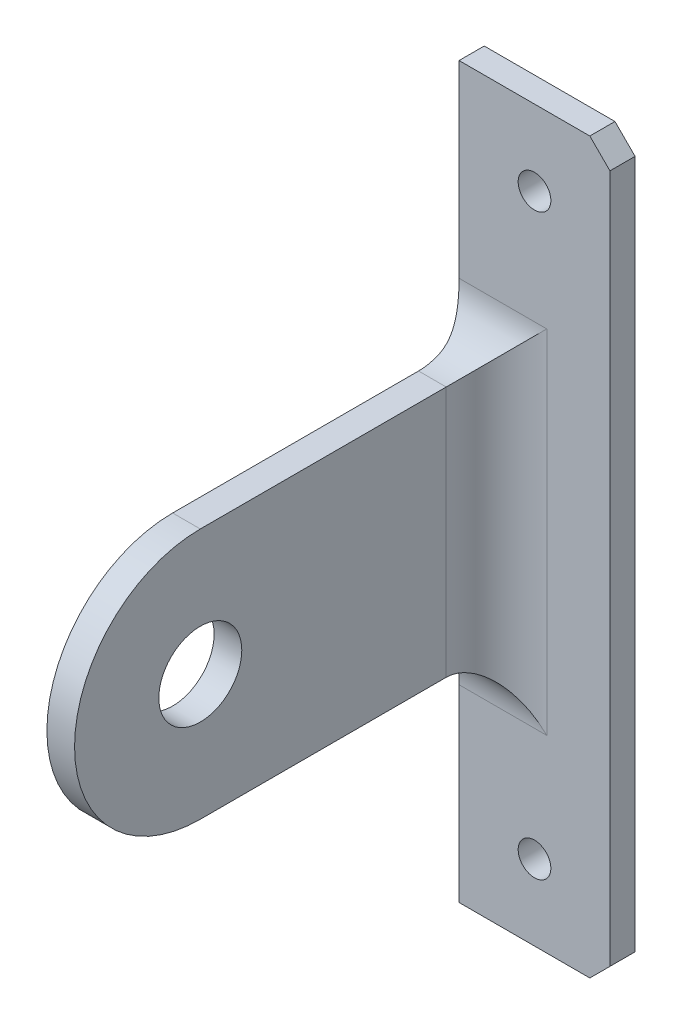
SolidWorks part; units mm, degrees
ref_plane "Front Plane" through (0, 0, 0) normal (0, 0, 1) x (1, 0, 0)
ref_plane "Top Plane" through (0, 0, 0) normal (0, 1, 0) x (1, 0, 0)
ref_plane "Right Plane" through (0, 0, 0) normal (1, 0, 0) x (0, 0, -1)
sketch "Sketch1" plane through (0, 0, 0) normal (1, 0, 0) x (0, 0, -1)
  line L1 (0, 12.5) -> (34.45, 12.5)
  line L2 (0, 4.125) -> (0, -12.5)
  line L3 (0, -12.5) -> (34.45, -12.5)
  line L4 (34.45, 12.5) -> (34.45, -12.5)
  circle A0 centre (0, 0) radius 4.125
  circle A1 centre (0, 0) radius 12.5 construction
  arc A2 (0, 12.5) -> (0, -12.5) centre (0, 0) ccw
  dimension "D1" = 8.25
  dimension "D2" = 25
  dimension "D3" = 34.45
extrude "Boss-Extrude1" add sketch "Sketch1" along normal blind 2.75 contours L1 A2 A0 L3 L4 region at (0, 0, -12.849)
sketch "Sketch2" [suppressed] plane through (0, 0, 0) normal (-1, 0, 0) x (0, 0, 1)
  circle A0 centre (0, 0) radius 1.5
  circle A1 centre (0, 0) radius 4.5
  dimension "D1" = 9
  dimension "D2" = 3
sketch "Sketch4" [suppressed] plane through (2.5, 0, 0) normal (1, 0, 0) x (0, 0, -1)
  circle A0 centre (0, 0) radius 2.5
sketch "Sketch5" [suppressed] plane through (2.5, 0, 0) normal (1, 0, 0) x (0, 0, -1)
  circle A0 centre (0, 0) radius 4.5
  circle A1 centre (0, 0) radius 2.5
  dimension "D1" = 9
  dimension "D2" = 5
sketch "Sketch6" plane through (0, 0, -34.45) normal (0, 0, -1) x (-1, 0, 0)
  line L1 (-8.8125, 36.25) -> (53.3216, 36.25)
  line L3 (6.25, -36.25) -> (53.3216, -36.25)
  line L4 (53.3216, 36.25) -> (53.3216, -36.25)
  line L6 (53.3216, -36.25) -> (-19.1784, 36.25) construction
  line L7 (6.25, -36.25) -> (-19.1784, -36.25)
  line L9 (-8.8125, 36.25) -> (-19.1784, 36.25)
  line L10 (-19.1784, -36.25) -> (-19.1784, 36.25)
  line L11 (53.3216, 36.25) -> (-19.1784, -36.25) construction
  point P4 (17.0716, 0)
  dimension "D1" = 72.5
  dimension "D2" = 72.5
extrude "Boss-Extrude4" add sketch "Sketch6" against normal blind 2.5
ref_plane "Plane1" through (-17.0716, 0, 0) normal (1, 0, 0) x (0, 0, -1)
ref_plane "Plane2" through (9.4784, 0, 0) normal (1, 0, 0) x (0, 0, -1)
sketch "Sketch7" plane through (0, 0, -31.95) normal (0, 0, 1) x (1, 0, 0)
  line L7 (1.7881, -3.3824) -> (-5.2119, -3.3824)
  line L12 (1.7881, -3.3824) -> (1.7881, -19.8824)
  line L18 (1.7881, -19.8824) -> (-5.2119, -19.8824)
  line L19 (-5.2119, -3.3824) -> (-5.2119, -19.8824)
  line L20 (1.7881, -3.3824) -> (-5.2119, -19.8824) construction
  line L21 (1.7881, -19.8824) -> (-5.2119, -3.3824) construction
  line L22 (-24.5, -4) -> (-8.5, -4)
  line L23 (-24.5, -4) -> (-24.5, 4)
  line L24 (-24.5, 4) -> (-8.5, 4)
  line L25 (-8.5, -4) -> (-8.5, 4)
  line L26 (-24.5, -4) -> (-8.5, 4) construction
  line L27 (-24.5, 4) -> (-8.5, -4) construction
  point P0 (-16.5, 0)
  point P2 (-1.7119, -11.6324)
  dimension "D1" = 16
  dimension "D2" = 16.5
  dimension "D3" = 7
  dimension "D4" = 8
extrude "Cut-Extrude2" cut sketch "Sketch7" against normal up to next
sketch "Sketch8" plane through (0, 0, 0) normal (0, 1, 0) x (1, 0, 0)
  line L10 (2.75, 4.125) -> (0, 4.125)
  line L15 (2.75, 4.125) -> (2.75, 31.95)
  line L16 (2.75, 31.95) -> (0, 31.95)
  line L21 (0, 4.125) -> (0, 31.95)
sketch "Sketch9" plane through (0, -12.5, 0) normal (0, -1, 0) x (1, 0, 0)
  line L0 (2.75, 0) -> (2.75, -31.95) construction
  line L1 (0, -31.95) -> (2.75, -31.95)
  line L2 (0, -31.95) -> (0, -9.5612)
  line L3 (0, -9.5612) -> (2.75, -9.5612)
  line L4 (2.75, -31.95) -> (2.75, -9.5612)
extrude "Cut-Extrude3" cut sketch "Sketch9" against normal up to next
extrude "Boss-Extrude5" add sketch "Sketch8" along normal mid plane 25
fillet "Fillet1" [suppressed] radius 4
fillet "Fillet2" radius 1 8 edges at (-5.2119, -3.3824, -33.2) (-5.2119, -19.8824, -33.2) (1.7881, -3.3824, -33.2) (-8.5, 4, -33.2) (1.7881, -19.8824, -33.2) (-8.5, -4, -33.2) (-24.5, 4, -33.2) (-24.5, -4, -33.2)
fillet "Fillet3" radius 4 4 edges at (19.1784, -36.25, -33.2) (19.1784, 36.25, -33.2) (-53.3216, 36.25, -33.2) (-53.3216, -36.25, -33.2)
sketch "Sketch10" plane through (0, 0, 0) normal (0, 1, 0) x (1, 0, 0)
  line L0 (15.1784, 31.95) -> (19.1784, 31.95) construction
  line L1 (21.7259, 31.95) -> (-56.5098, 31.95)
  line L2 (21.7259, 31.95) -> (21.7259, 38.24)
  line L3 (21.7259, 38.24) -> (-56.5098, 38.24)
  line L4 (-56.5098, 31.95) -> (-56.5098, 38.24)
extrude "Cut-Extrude4" cut sketch "Sketch10" against normal through all both and the other way through all
sketch "Sketch11" plane through (0, 0, 0) normal (0, 1, 0) x (1, 0, 0)
  line L1 (14.03, 31.95) -> (-0.97, 31.95)
  line L2 (14.03, 31.95) -> (14.03, 29.45)
  line L3 (14.03, 29.45) -> (-0.97, 29.45)
  line L4 (-0.97, 31.95) -> (-0.97, 29.45)
  line L6 (2.75, 31.95) -> (0, 31.95) construction
  line L7 (0, 31.95) -> (0, 0) construction
  dimension "D1" = 2.5
  dimension "D2" = 15
  dimension "D3" = 0.97
extrude "Boss-Extrude6" add sketch "Sketch11" along normal mid plane 25
sketch "Sketch12" plane through (0, 0, -31.95) normal (0, 0, -1) x (-1, 0, 0)
  line L0 (55, 0) -> (-55, 0) construction
  line L1 (-14.03, 36.25) -> (58.47, 36.25) construction
  line L2 (-14.03, 36.25) -> (-14.03, -36.25) construction
  line L3 (-14.03, -36.25) -> (58.47, -36.25) construction
  line L4 (58.47, 36.25) -> (58.47, -36.25) construction
  line L5 (-14.03, 36.25) -> (58.47, -36.25) construction
  line L6 (58.47, 36.25) -> (-14.03, -36.25) construction
  line L7 (-14.03, 12.5) -> (-14.03, -12.5) construction
  circle A0 centre (-6.53, 28.75) radius 1.5
  circle A1 centre (-6.53, -28.75) radius 1.5
  circle A2 centre (-6.53, 28.75) radius 3
  circle A3 centre (-6.53, -28.75) radius 3
  point P4 (-14.03, 0)
  dimension "D3" = 3
  dimension "D5" = 6
  dimension "D1" = 72.5
  dimension "D2" = 72.5
  dimension "D4" = 7.5
sketch "Sketch13" plane through (0, 0, -31.95) normal (0, 0, -1) x (-1, 0, 0)
  line L0 (-14.03, 12.5) -> (0.97, 12.5) construction
  line L1 (-14.03, 12.5) -> (0.97, 12.5)
  line L2 (-14.03, 12.5) -> (-14.03, 32.25)
  line L4 (0.97, 12.5) -> (0.97, 36.25)
  line L5 (0.97, 36.25) -> (-10.03, 36.25)
  line L6 (-14.03, 32.25) -> (-14.03, 36.25)
  line L7 (-14.03, 36.25) -> (-10.03, 36.25)
  dimension "D1" = 4
  dimension "D3" = 15
  dimension "D4" = 36.25
  dimension "D5" = 4
extrude "Boss-Extrude7" add sketch "Sketch13" against normal blind 2.5
mirror "Mirror1" about plane through (0, 0, 0) normal (0, 1, 0) of "Boss-Extrude6", "Boss-Extrude7"
sketch "Sketch14" plane through (0, 0, -31.95) normal (0, 0, -1) x (-1, 0, 0)
  line L1 (0.97, -36.25) -> (0.97, 36.25) construction
  line L2 (0.97, 36.25) -> (-14.03, 36.25) construction
  circle A0 centre (-6.53, 28.75) radius 1.625
  dimension "D3" = 3.25
  dimension "D1" = 7.5
  dimension "D2" = 7.5
extrude "Cut-Extrude5" cut sketch "Sketch14" against normal blind 2.5
sketch "Sketch15" [suppressed] plane through (0, 0, -31.95) normal (0, 0, -1) x (-1, 0, 0)
  circle A0 centre (-6.4288, 28.75) radius 2.5
  circle A1 centre (-6.4288, 28.75) radius 4
  dimension "D1" = 8
  dimension "D2" = 5
extrude "Boss-Extrude8" [suppressed] add sketch "Sketch15" against normal blind 6
mirror "Mirror2" about plane through (0, 0, 0) normal (0, 1, 0) of "Cut-Extrude5", "Boss-Extrude8"
fillet "Fillet4" radius 5 4 edges at (1.375, -12.5, -29.45) (0, 0, -29.45) (1.375, 12.5, -29.45) (2.75, 0, -29.45)
chamfer "Chamfer1" distance 2 angle 45 2 edges at (14.03, -36.25, -30.7) (14.03, 36.25, -30.7)
